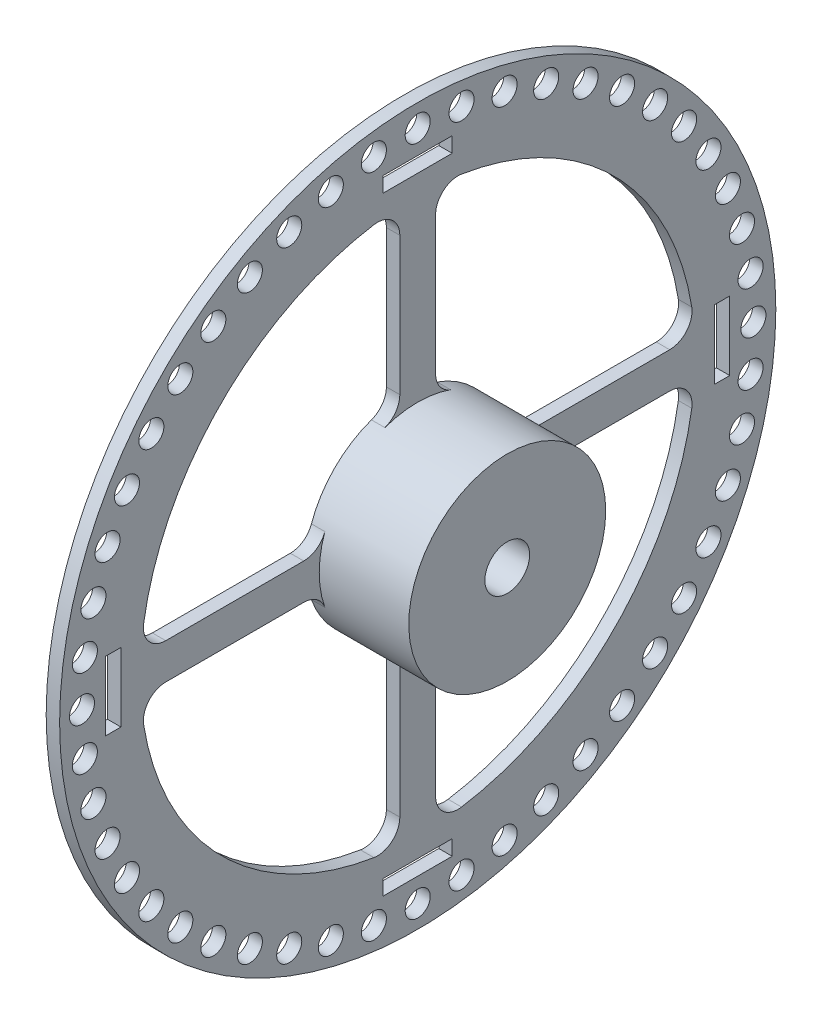
SolidWorks part; units mm, degrees
material "AISI 304"
ref_plane "Front Plane" through (0, 0, 0) normal (0, 0, 1) x (1, 0, 0)
ref_plane "Top Plane" through (0, 0, 0) normal (0, 1, 0) x (1, 0, 0)
ref_plane "Right Plane" through (0, 0, 0) normal (1, 0, 0) x (0, 0, -1)
sketch "Sketch3" plane through (0, 0, 0) normal (1, 0, 0) x (0, 0, -1)
  line L0 (10.8167, 2) -> (30.9354, 2)
  line L9 (-30.9354, 2) -> (-10.8167, 2)
  line L11 (-30.9354, -2) -> (-10.8167, -2)
  line L13 (10.8167, -2) -> (30.9354, -2)
  line L14 (-2, -10.8167) -> (-2, -30.9354)
  line L16 (-2, 30.9354) -> (-2, 10.8167)
  line L18 (2, 30.9354) -> (2, 10.8167)
  line L19 (2, -10.8167) -> (2, -30.9354)
  line L20 (0, 0) -> (0, 40) construction
  line L22 (3.85, 34.85) -> (-3.85, 34.85)
  line L23 (3.85, 34.85) -> (3.85, 33.15)
  line L24 (3.85, 33.15) -> (-3.85, 33.15)
  line L25 (-3.85, 34.85) -> (-3.85, 33.15)
  line L26 (3.85, 34.85) -> (-3.85, 33.15) construction
  line L27 (3.85, 33.15) -> (-3.85, 34.85) construction
  line L39 (33.15, -3.85) -> (33.15, 3.85)
  line L40 (34.85, 3.85) -> (33.15, 3.85)
  line L41 (34.85, -3.85) -> (34.85, 3.85)
  line L42 (34.85, -3.85) -> (33.15, -3.85)
  line L43 (-3.85, -33.15) -> (3.85, -33.15)
  line L44 (3.85, -34.85) -> (3.85, -33.15)
  line L45 (-3.85, -34.85) -> (3.85, -34.85)
  line L46 (-3.85, -34.85) -> (-3.85, -33.15)
  line L47 (-33.15, 3.85) -> (-33.15, -3.85)
  line L48 (-34.85, -3.85) -> (-33.15, -3.85)
  line L49 (-34.85, 3.85) -> (-34.85, -3.85)
  line L50 (-34.85, 3.85) -> (-33.15, 3.85)
  circle A0 centre (0, 0) radius 40
  arc A1 (30.9354, 2) -> (2, 30.9354) centre (0, 0) ccw
  arc A2 (10.8167, 2) -> (2, 10.8167) centre (0, 0) ccw
  arc A3 (-10.8167, -2) -> (-2, -10.8167) centre (0, 0) ccw
  arc A4 (-30.9354, -2) -> (-2, -30.9354) centre (0, 0) ccw
  arc A5 (2, -30.9354) -> (30.9354, -2) centre (0, 0) ccw
  arc A6 (2, -10.8167) -> (10.8167, -2) centre (0, 0) ccw
  arc A7 (-2, 10.8167) -> (-10.8167, 2) centre (0, 0) ccw
  arc A8 (-2, 30.9354) -> (-30.9354, 2) centre (0, 0) ccw
  circle A9 centre (0, 0) radius 3
  point P20 (0, 34)
  point P41 (1.15, 0)
  point P42 (0, 0)
  dimension "D1" = 80
  dimension "D2" = 62
  dimension "D5" = 22
  dimension "D8" = 6
  dimension "D3" = 4
  dimension "D4" = 2
  dimension "D6" = 2
  dimension "D7" = 4
  dimension "D9" = 6
  dimension "D10" = 7.7
  dimension "D11" = 1.7
  dimension "D12" = 4
extrude "Boss-Extrude2" add sketch "Sketch3" along normal blind 1.5
sketch "Sketch4" plane through (0, 0, 0) normal (-1, 0, 0) x (0, 0, 1)
  line L0 (0, 0) -> (0, 37.5) construction
  circle A0 centre (0, 37.5) radius 1.4
  point P2 (0, 21.5438)
  dimension "D1" = 2.8
  dimension "D2" = 37.5
extrude "Cut-Extrude1" cut sketch "Sketch4" against normal blind 1.5 contours A0
pattern_circular "CirPattern1" count 48 over 360 about axis through (0, 0, 0) along (1, 0, 0) of "Cut-Extrude1"
fillet "Fillet1" radius 2.5 15 edges at (0.75, -2, 30.9354) (0.75, -30.9354, 2) (0.75, -10.8167, 2) (0.75, -2, 10.8167) (0.75, -30.9354, -2) (0.75, -2, -30.9354) (0.75, 2, -10.8167) (0.75, 2, -30.9354) (0.75, 2, 10.8167) (0.75, 2, 30.9354) (0.75, 10.8167, 2) (0.75, 30.9354, 2) (0.75, 10.8167, -2) (0.75, 30.9354, -2) (0.75, -2, -10.8167)
sketch "Sketch5" plane through (1.5, 0, 0) normal (1, 0, 0) x (0, 0, -1)
  circle A0 centre (0, 0) radius 11
  circle A1 centre (0, 0) radius 2.5
  dimension "D1" = 5
  dimension "D2" = 22
extrude "Boss-Extrude4" add sketch "Sketch5" along normal blind 10
